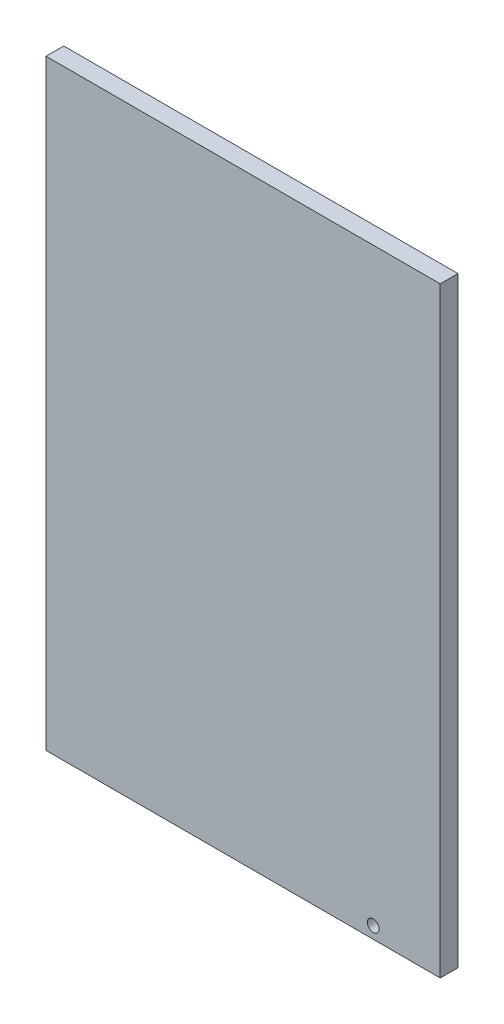
SolidWorks part; units mm, degrees
ref_plane "Front Plane" through (0, 0, 0) normal (0, 0, 1) x (1, 0, 0)
ref_plane "Top Plane" through (0, 0, 0) normal (0, 1, 0) x (1, 0, 0)
ref_plane "Right Plane" through (0, 0, 0) normal (1, 0, 0) x (0, 0, -1)
sketch "Sketch1" plane through (0, 0, 0) normal (0, 0, 1) x (1, 0, 0)
  line L1 (-100, -152.5) -> (100, -152.5)
  line L2 (-100, -152.5) -> (-100, 152.5)
  line L3 (-100, 152.5) -> (100, 152.5)
  line L4 (100, -152.5) -> (100, 152.5)
  line L5 (-100, -152.5) -> (100, 152.5) construction
  line L6 (-100, 152.5) -> (100, -152.5) construction
  point P0 (0, 0)
  dimension "D1" = 200
  dimension "D2" = 305
extrude "Boss-Extrude1" add sketch "Sketch1" along normal blind 9
sketch "Sketch2" plane through (0, 0, 9) normal (0, 0, 1) x (1, 0, 0)
  line L0 (100, -152.5) -> (100, 152.5) construction
  line L1 (-100, -152.5) -> (100, -152.5) construction
  circle A0 centre (66, -146.5) radius 3
  dimension "D1" = 6
  dimension "D2" = 34
  dimension "D3" = 6
extrude "Cut-Extrude1" cut sketch "Sketch2" against normal through all
sketch "Sketch3" [suppressed] plane through (0, 0, 0) normal (0, 0, -1) x (-1, 0, 0)
  line L0 (-120.2594, -152.5) -> (119.7406, -152.5) construction
  line L2 (-90.2594, -139.5) -> (-30.2594, -139.5) construction
  line L3 (-30.2594, -139.5) -> (29.7406, -139.5) construction
  line L4 (29.7406, -139.5) -> (89.7406, -139.5) construction
  circle A0 centre (-90.2594, -139.5) radius 4.75
  circle A1 centre (-30.2594, -139.5) radius 5.5875
  circle A2 centre (29.7406, -139.5) radius 5.5875
  circle A3 centre (89.7406, -139.5) radius 4.75
  point P3 (-0.2594, -152.5)
  dimension "D2" = 9.5
  dimension "D7" = 11.175
  dimension "D1" = 240
  dimension "D3" = 13
  dimension "D4" = 30
  dimension "D5" = 60
  dimension "D6" = 60
  dimension "60" = 60
extrude "Cut-Extrude2" [suppressed] cut sketch "Sketch3" against normal through all
equation "\"PCLength\"= 320mm'Length across I/O from PS to GPU"
equation "\"PCWidth\"= 242mm'Distance of longest part parallel to GPU(ussually GPU)"
equation "\"PCHeight\"= 172mm'Tallest point with mobo laying flat"
equation "\"WallThickness\"= 9mm'Thickness of each outer tank wall"
equation "\"ThermoBarrierThickness\"= 3mm'Thickness of barrier between hot side and cold side"
equation "\"HotSideGap\"= 25mm'Space in the hot side for a pump"
equation "\"PCClearance\"= 30mm'Clearance from top of tank to top of PC"
equation "\"RadiatorHeight\"= 275mm'Final Height from ground of radiators"
equation "\"D1@Sketch1\"=\"PCHeight\" + \"ThermoBarrierThickness\" + \"HotSideGap\""
equation "\"D2@Sketch1\"=\"RadiatorHeight\" + \"PCClearance\""
equation "\"D1@Boss-Extrude1\"=\"WallThickness\""
equation "\"D2@Sketch2\"=\"HotSideGap\" + \"ThermoBarrierThickness\" + 6"
